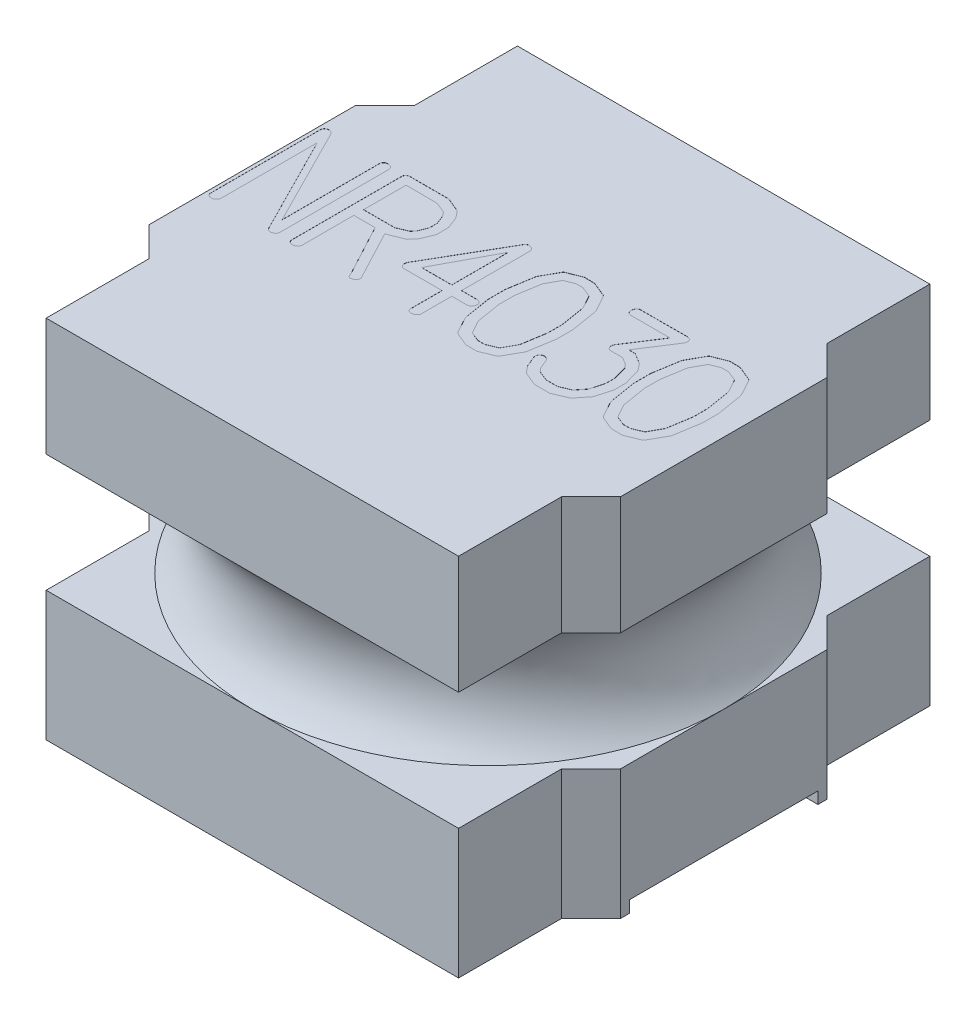
SolidWorks part; units mm, degrees
ref_plane "Front Plane" through (0, 0, 0) normal (0, 0, 1) x (1, 0, 0)
ref_plane "Top Plane" through (0, 0, 0) normal (0, 1, 0) x (1, 0, 0)
ref_plane "Right Plane" through (0, 0, 0) normal (1, 0, 0) x (0, 0, -1)
sketch "Sketch1" plane through (0, 0, 0) normal (0, 1, 0) x (1, 0, 0)
  line L0 (-2, 0) -> (2, 0) construction
  line L1 (-1.75, 2) -> (1.75, 2)
  line L2 (-2, 0.875) -> (-2, -0.875)
  line L3 (-1.75, -2) -> (1.75, -2)
  line L4 (2, 0.875) -> (2, -0.875)
  line L5 (-1.75, 1.75) -> (1.75, -1.75) construction
  line L6 (-1.75, -1.75) -> (1.75, 1.75) construction
  line L7 (0, 2) -> (0, -2) construction
  line L8 (-1.75, 2) -> (-1.75, 1.125)
  line L9 (-1.75, 1.125) -> (-2, 0.875)
  line L10 (1.75, 2) -> (1.75, 1.125)
  line L11 (1.75, 1.125) -> (2, 0.875)
  line L12 (1.75, -2) -> (1.75, -1.125)
  line L13 (1.75, -1.125) -> (2, -0.875)
  line L14 (-1.75, -1.125) -> (-2, -0.875)
  line L15 (-1.75, -2) -> (-1.75, -1.125)
  line L16 (-2, -0.875) -> (-2, -2) construction
  line L17 (-2, -2) -> (-1.75, -1.75) construction
  line L18 (-2, -2) -> (-1.75, -2) construction
  line L19 (1.75, -2) -> (2, -2) construction
  line L20 (1.75, -1.75) -> (2, -2) construction
  line L21 (2, -0.875) -> (2, -2) construction
  line L22 (2, 2) -> (2, 0.875) construction
  line L23 (1.75, 1.75) -> (2, 2) construction
  line L24 (1.75, 2) -> (2, 2) construction
  line L25 (-2, 2) -> (-1.75, 2) construction
  line L26 (-2, 2) -> (-1.75, 1.75) construction
  line L27 (-2, 2) -> (-2, 0.875) construction
  point P0 (0, 0)
  point P22 (1.75, 1.1699)
  point P27 (0, 0)
  point P28 (0, 0)
  point P29 (0, 0)
  point P30 (0, 0)
  dimension "D1" = 4
  dimension "D2" = 3.5
  dimension "D3" = 1.75
  dimension "D4" = 135
  dimension "D5" = 4
extrude "Boss-Extrude1" add sketch "Sketch1" along normal blind 1 from offset 1.5 offset against normal yes
sketch "Sketch2" plane through (0, 0, 0) normal (1, 0, 0) x (0, 0, -1)
  line L0 (0, -1.5) -> (0, 0) construction
  line L1 (-0.875, -1.5) -> (0.875, -1.5) construction
  line L2 (-2, 0.5) -> (0, 0.5)
  line L3 (0, 0.5) -> (0, -0.5)
  line L4 (0, -0.5) -> (-2, -0.5)
  arc A0 (-2, -0.5) -> (-2, 0.5) centre (-2.559, 0) ccw
  point P8 (0, 0)
  point P12 (-2, -0.5)
  dimension "D2" = 0.75
  dimension "D1" = 1
revolve "Revolve1" add sketch "Sketch2" angle 360 about L0
mirror "Mirror1" about plane through (0, 0, 0) normal (0, 1, 0) of "Boss-Extrude1"
sketch "Sketch3" plane through (0, 1.5, 0) normal (0, 1, 0) x (1, 0, 0)
  line L0 (-2, -0.3915) -> (2, -0.3915) construction
  text T0 "NR4030" font "SWSimp" height 1
  point P5 (0, 0)
  point P6 (0, 0)
  point P7 (0, 0)
  point P8 (0, 0)
extrude "Cut-Extrude1" cut sketch "Sketch3" against normal blind 0.001
sketch "Sketch4" plane through (0, -1.5, 0) normal (0, -1, 0) x (1, 0, 0)
  line L0 (-2, 0.8) -> (2, 0.8)
  line L1 (-2, -0.875) -> (-2, 0.875) construction
  line L2 (2, 0.875) -> (2, -0.875) construction
  line L3 (0, 0) -> (2.4671, 0) construction
  line L4 (2, 0.8) -> (2, 0.875)
  line L5 (2, 0.875) -> (1.75, 1.125)
  line L6 (1.75, 1.125) -> (1.75, 2)
  line L7 (1.75, 2) -> (-1.75, 2)
  line L8 (-1.75, 2) -> (-1.75, 1.125)
  line L9 (-1.75, 1.125) -> (-2, 0.875)
  line L10 (-2, 0.875) -> (-2, 0.8)
  line L11 (-1.75, -1.125) -> (-2, -0.875)
  line L12 (-1.75, -2) -> (-1.75, -1.125)
  line L13 (1.75, -2) -> (-1.75, -2)
  line L14 (1.75, -1.125) -> (1.75, -2)
  line L15 (2, -0.875) -> (1.75, -1.125)
  line L16 (2, -0.8) -> (2, -0.875)
  line L17 (-2, -0.8) -> (2, -0.8)
  line L18 (-2, -0.875) -> (-2, -0.8)
  dimension "D1" = 0.8
extrude "Boss-Extrude2" add sketch "Sketch4" along normal blind 0.1
